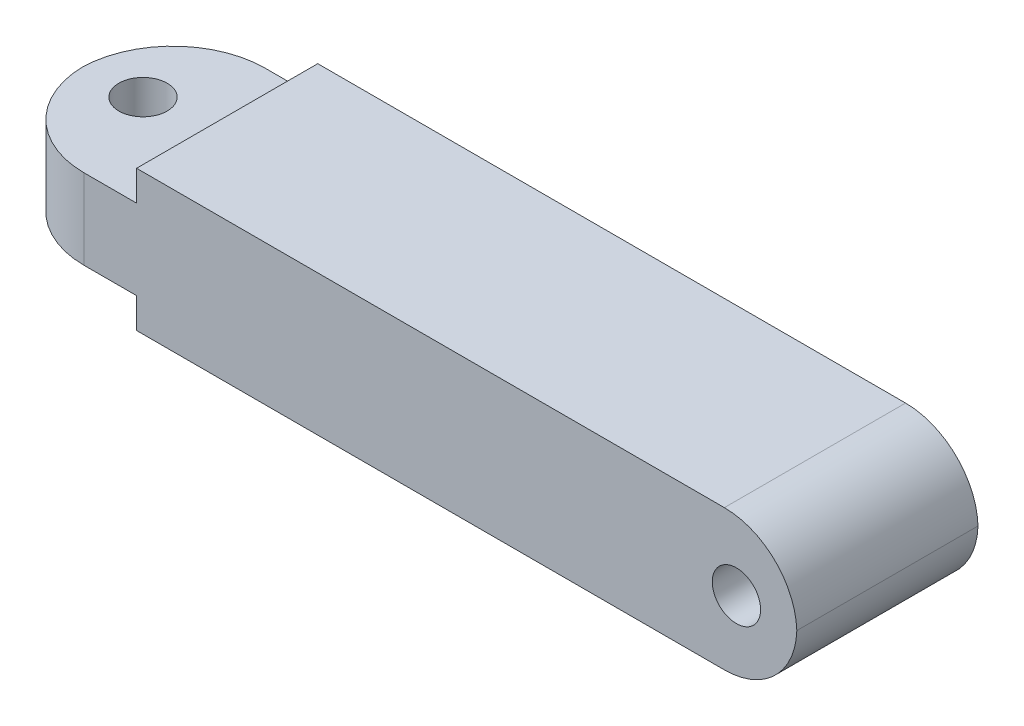
SolidWorks part; units mm, degrees
material "Balsa"
ref_plane "Front Plane" through (0, 0, 0) normal (0, 0, 1) x (1, 0, 0)
ref_plane "Top Plane" through (0, 0, 0) normal (0, 1, 0) x (1, 0, 0)
ref_plane "Right Plane" through (0, 0, 0) normal (1, 0, 0) x (0, 0, -1)
sketch "Sketch1" plane through (0, 0, 0) normal (0, 1, 0) x (1, 0, 0)
  line L1 (-86.8269, 18.0401) -> (113.1731, 18.0401)
  line L2 (-86.8269, 18.0401) -> (-86.8269, -26.9599)
  line L3 (-86.8269, -26.9599) -> (113.1731, -26.9599)
  line L4 (113.1731, 18.0401) -> (113.1731, -26.9599)
  dimension "D1" = 200
  dimension "D2" = 45
extrude "Boss-Extrude1" add sketch "Sketch1" along normal mid plane 34.9
fillet "Fillet1" radius 18 2 edges at (113.1731, -17.45, 4.4599) (113.1731, 17.45, 4.4599)
fillet "Fillet2" radius 23 2 edges at (-86.8269, 0, -18.0401) (-86.8269, 0, 26.9599)
sketch "Sketch2" plane through (0, 17.45, 0) normal (0, 1, 0) x (1, 0, 0)
  line L0 (95.1731, 18.0401) -> (-63.8269, 18.0401) construction
  line L1 (-50.8214, 18.0401) -> (-90.8214, 18.0401)
  line L2 (-50.8214, 18.0401) -> (-50.8214, -26.9599)
  line L3 (-50.8214, -26.9599) -> (-90.8214, -26.9599)
  line L4 (-90.8214, 18.0401) -> (-90.8214, -26.9599)
  dimension "D1" = 45
  dimension "D2" = 40
  dimension "D3" = 36
extrude "Cut-Extrude1" cut sketch "Sketch2" against normal blind 7.5
mirror "Mirror1" about plane through (0, 0, 0) normal (0, 1, 0) of "Cut-Extrude1"
sketch "Sketch3" plane through (0, 9.95, 0) normal (0, 1, 0) x (1, 0, 0)
  circle A0 centre (-72.8214, -3.3564) radius 6
  dimension "D1" = 12
  dimension "D2" = 14
extrude "Cut-Extrude2" cut sketch "Sketch3" against normal through all
sketch "Sketch4" plane through (0, 0, 26.9599) normal (0, 0, 1) x (1, 0, 0)
  circle A0 centre (98.1647, 0) radius 6
  dimension "D1" = 12
  dimension "D2" = 15
extrude "Cut-Extrude3" cut sketch "Sketch4" against normal through all
scale "Scale1" bodies to scale 105 scale about origin uniform scaling yes scale factor 0.31
